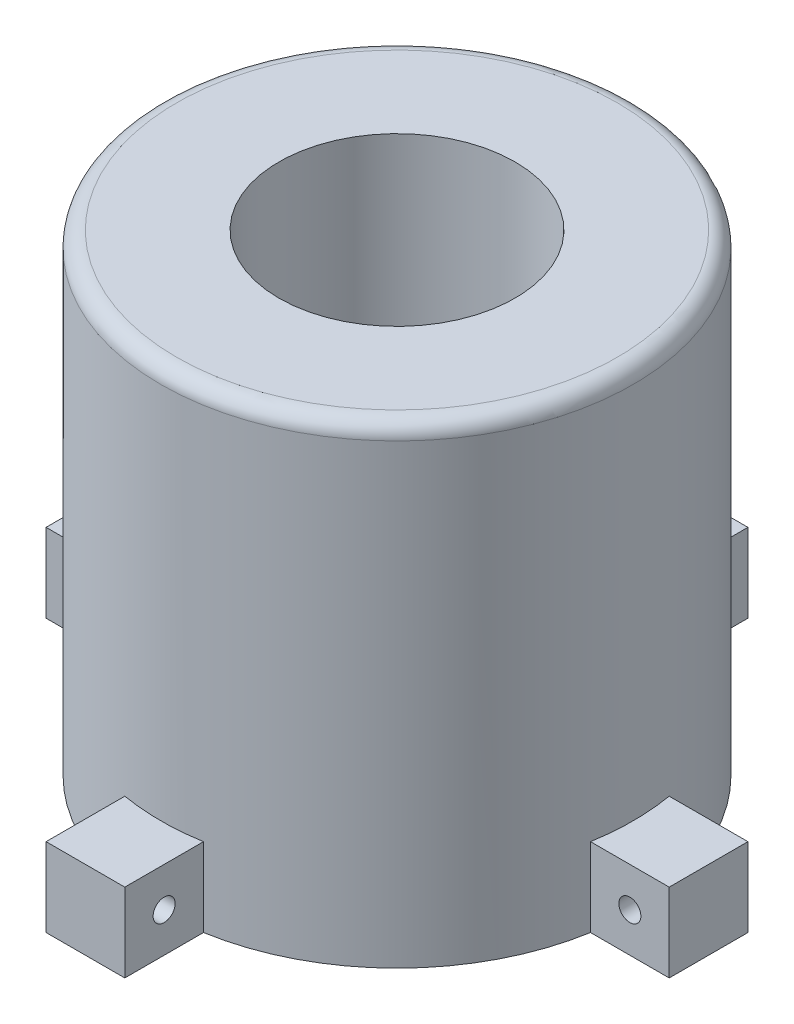
SolidWorks part; units mm, degrees
ref_plane "Front Plane" through (0, 0, 0) normal (0, 0, 1) x (1, 0, 0)
ref_plane "Top Plane" through (0, 0, 0) normal (0, 1, 0) x (1, 0, 0)
ref_plane "Right Plane" through (0, 0, 0) normal (1, 0, 0) x (0, 0, -1)
sketch "Sketch2" plane through (0, 0, 0) normal (0, 1, 0) x (1, 0, 0)
  circle A0 centre (0, 0) radius 38.1
  dimension "D1" = 76.2
extrude "Boss-Extrude1" add sketch "Sketch2" along normal blind 76.2
sketch "Sketch3" plane through (0, 76.2, 0) normal (0, 1, 0) x (1, 0, 0)
  circle A0 centre (0, 0) radius 19.05
  dimension "D1" = 38.1
extrude "Cut-Extrude1" cut sketch "Sketch3" against normal blind 76.2
fillet "Fillet1" radius 2.54 1 edges at (0, 76.2, 38.1)
sketch "Sketch4" plane through (0, 0, 0) normal (0, 1, 0) x (1, 0, 0)
  line L0 (-37.5671, 6.35) -> (-50.2671, 6.35)
  line L1 (-50.2671, 6.35) -> (-50.2671, -6.35)
  line L2 (-50.2671, -6.35) -> (-37.5671, -6.35)
  arc A0 (-37.5671, 6.35) -> (-37.5671, -6.35) centre (0, 0) ccw
  circle A1 centre (0, 0) radius 38.1 construction
  dimension "D1" = 12.7
  dimension "D2" = 12.7
  dimension "D3" = 12.7
extrude "Boss-Extrude2" add sketch "Sketch4" along normal blind 12.7
sketch "Sketch5" plane through (0, 0, 6.35) normal (0, 0, 1) x (1, 0, 0)
  line L0 (-50.2671, 12.7) -> (-37.5671, 12.7) construction
  line L1 (-50.2671, 12.7) -> (-50.2671, 0) construction
  circle A0 centre (-43.9171, 6.35) radius 1.778
  point P4 (-43.9171, 12.7)
  point P7 (-50.2671, 6.35)
  dimension "D1" = 3.556
extrude "Cut-Extrude2" cut sketch "Sketch5" against normal blind 25.4
pattern_circular "CirPattern2" count 4 over 360 about axis through (0, 76.2, 0) along (0, -1, 0) of "Boss-Extrude2", "Cut-Extrude2" reverse direction yes
